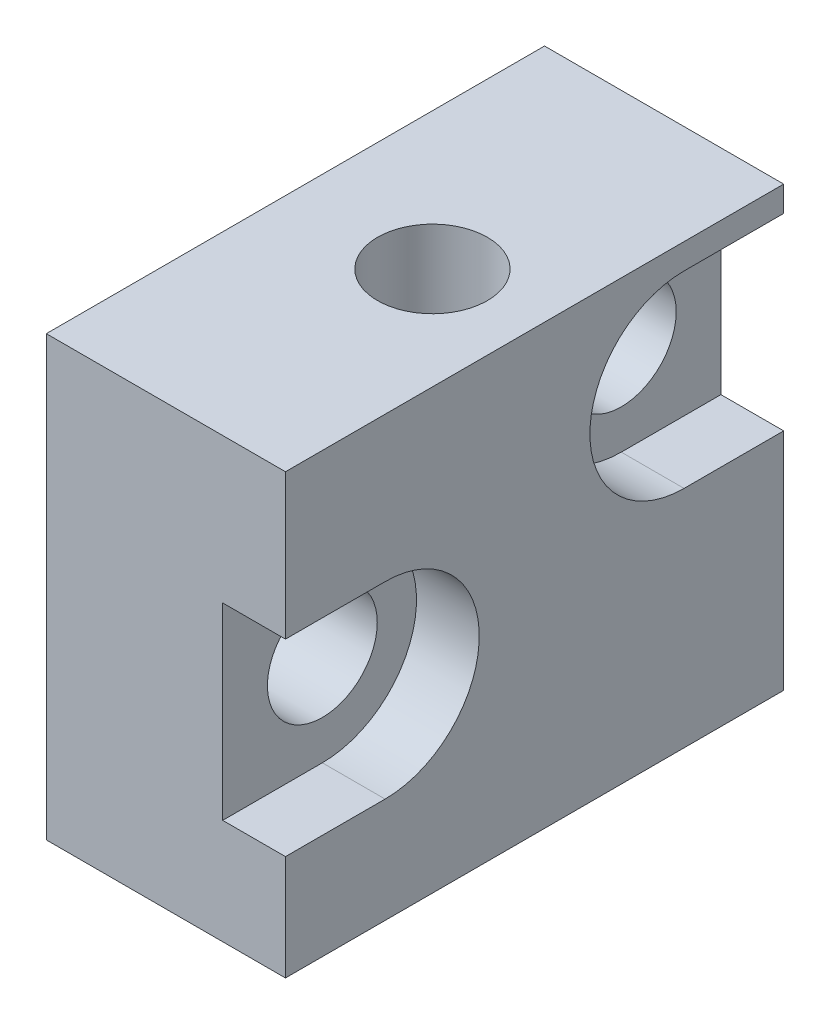
SolidWorks part; units mm, degrees
other "Markup1"
sketch "Sketch9"
material "PET"
ref_plane "Front Plane" through (0, 0, 0) normal (1, 0, 0) x (0, 1, 0)
ref_plane "Top Plane" through (0, 0, 0) normal (0, 0, 1) x (0, 1, 0)
ref_plane "Right Plane" through (0, 0, 0) normal (0, 1, 0) x (-1, 0, 0)
sketch "Sketch1" plane through (0, 0, 0) normal (1, 0, 0) x (0, 1, 0)
  line L1 (5.715, -7.9375) -> (-5.715, -7.9375)
  line L2 (5.715, -7.9375) -> (5.715, 7.9375)
  line L3 (5.715, 7.9375) -> (-5.715, 7.9375)
  line L4 (-5.715, -7.9375) -> (-5.715, 7.9375)
  line L5 (5.715, -7.9375) -> (-5.715, 7.9375) construction
  line L6 (5.715, 7.9375) -> (-5.715, -7.9375) construction
  point P0 (0, 0)
  dimension "D1" = 15.875
  dimension "D2" = 11.43
extrude "Boss-Extrude1" add sketch "Sketch1" along normal blind 7.62
sketch "Sketch3" plane through (0, -5.715, 0) normal (0, -1, 0) x (1, 0, 0)
  line L10 (0, 7.9375) -> (0, -7.9375)
  line L11 (0, -7.9375) -> (7.62, -7.9375)
  line L12 (7.62, -7.9375) -> (7.62, 7.9375)
  line L13 (7.62, 7.9375) -> (0, 7.9375)
  line L14 (0, 7.9375) -> (0, -7.9375)
  line L15 (0, -7.9375) -> (7.62, -7.9375)
  line L16 (7.62, -7.9375) -> (7.62, 7.9375)
  line L17 (7.62, 7.9375) -> (0, 7.9375)
  circle A0 centre (4.3663, 0) radius 1.75
  circle A1 centre (4.3663, 0) radius 5 construction
  circle A2 centre (4.3663, 0) radius 3 construction
  point P2 (9.3663, 0)
  point P3 (2.6163, 0)
  point P6 (-6.35, 0)
  dimension "D1" = 3.5
  dimension "D2" = 10
  dimension "D6" = 6
  dimension "D3" = 15.7163
  dimension "D4" = 6.35
  dimension "D5" = 0
extrude "Cut-Extrude1" cut sketch "Sketch3" against normal blind 22.2885 contours A0 region at (4.3663, -5.715, 0)
sketch "Sketch4" plane through (7.62, 0, 0) normal (1, 0, 0) x (0, 1, 0)
  line L0 (-5.715, 7.9375) -> (-5.715, -7.9375) construction
  line L1 (1.905, -4.7625) -> (-1.905, -4.7625) construction
  line L2 (1.905, -4.7625) -> (1.905, 4.7625) construction
  line L3 (1.905, 4.7625) -> (-1.905, 4.7625) construction
  line L4 (-1.905, -4.7625) -> (-1.905, 4.7625) construction
  line L5 (1.905, -4.7625) -> (-1.905, 4.7625) construction
  line L6 (1.905, 4.7625) -> (-1.905, -4.7625) construction
  line L7 (5.715, 7.9375) -> (-5.715, 7.9375) construction
  circle A5 centre (-1.905, 4.7625) radius 1.75
  circle A6 centre (1.905, -4.7625) radius 1.75
  point P0 (0, 0)
  dimension "D3" = 3.5
  dimension "D1" = 3.81
  dimension "D2" = 3.175
extrude "Cut-Extrude2" cut sketch "Sketch4" against normal blind 22.2885 contours A5 | A6 region at (7.62, -1.905, 4.7625) region at (7.62, 1.905, -4.7625)
sketch "Sketch5" plane through (7.62, 0, 0) normal (1, 0, 0) x (0, 1, 0)
  line L0 (-4.905, 4.7625) -> (-4.905, 7.9375)
  line L1 (5.715, 7.9375) -> (-5.715, 7.9375) construction
  line L2 (-4.905, 7.9375) -> (1.095, 7.9375)
  line L3 (1.095, 7.9375) -> (1.095, 4.7625)
  line L4 (4.905, -4.7625) -> (4.905, -7.9375)
  line L5 (-5.715, -7.9375) -> (5.715, -7.9375) construction
  line L6 (4.905, -7.9375) -> (-1.095, -7.9375)
  line L7 (-1.095, -7.9375) -> (-1.095, -4.7625)
  line L8 (-1.905, 1.7625) -> (-5.715, 1.7625)
  line L9 (-5.715, 7.9375) -> (-5.715, -7.9375) construction
  circle A0 centre (1.905, -4.7625) radius 1.75 construction
  circle A1 centre (-1.905, 4.7625) radius 1.75 construction
  circle A2 centre (1.905, -4.7625) radius 1.75 construction
  circle A3 centre (-1.905, 4.7625) radius 1.75 construction
  circle A4 centre (-1.905, 4.7625) radius 3
  circle A5 centre (1.905, -4.7625) radius 3
  circle M3 centre (-1.905, 4.7625) radius 1.75
  circle M4 centre (1.905, -4.7625) radius 1.75
  line M6 (-5.715, -7.9375) -> (5.715, -7.9375)
  line M8 (5.715, 7.9375) -> (-5.715, 7.9375)
  dimension "D1" = 6
extrude "Cut-Extrude3" cut sketch "Sketch5" against normal blind 2 contours A4 M3 | A4 L3 L0 M8 | A5 M4 | A5 L7 L4 M6 region at (7.62, -4.8371, 6.35) region at (7.62, -1.905, 7.6776) region at (7.62, 1.905, -7.6776) region at (7.62, 4.8371, -6.35)
sketch "Sketch6" plane through (7.62, 0, 0) normal (1, 0, 0) x (0, 1, 0)
  line L0 (-5.715, -7.9375) -> (-1.095, -7.9375) construction
  line L1 (-5.715, 7.9375) -> (-8.255, 7.9375)
  line L2 (-5.715, 7.9375) -> (-5.715, -7.9375)
  line L3 (-5.715, -7.9375) -> (-8.255, -7.9375)
  line L4 (-8.255, 7.9375) -> (-8.255, -7.9375)
  point P5 (0, 0)
  dimension "D1" = 2.54
extrude "Boss-Extrude2" add sketch "Sketch6" against normal up to vertex (7.62 mm away) up to point (0, -5.715, 7.9375)
sketch "Sketch8" plane through (0, 5.715, 0) normal (0, 1, 0) x (-1, 0, 0)
  circle A0 centre (-4.3663, 0) radius 1.75 construction
  circle A1 centre (-4.3663, 0) radius 1.75
extrude "Cut-Extrude4" cut sketch "Sketch8" against normal blind 18.796
